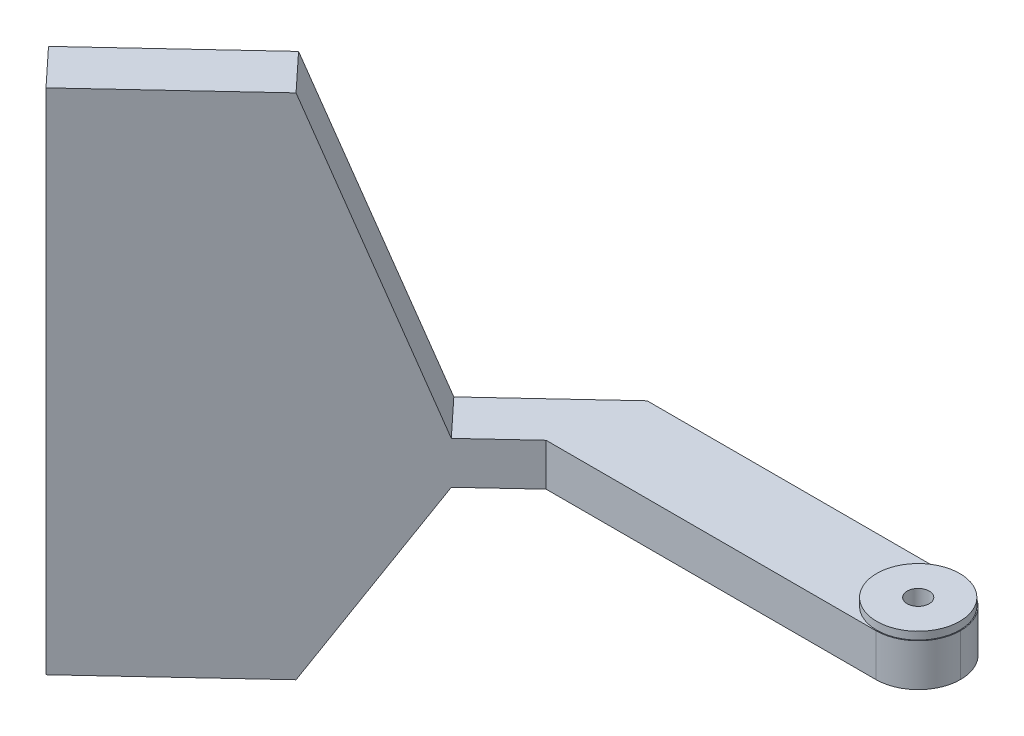
SolidWorks part; units mm, degrees
ref_plane "Front" through (0, 0, 0) normal (0, 0, 1) x (1, 0, 0)
ref_plane "Top" through (0, 0, 0) normal (0, 1, 0) x (1, 0, 0)
ref_plane "Right" through (0, 0, 0) normal (1, 0, 0) x (0, 0, -1)
sketch "Sketch1" plane through (0, 0, 0) normal (0, 1, 0) x (1, 0, 0)
  line L0 (0, 10) -> (0, 0)
  line L1 (0, 0) -> (42, 0)
  line L3 (0, 10) -> (42, 10)
  line L4 (42, 0) -> (42, 10)
  line L9 (0, 10) -> (-36.5677, -24.0999)
  line L10 (-36.5677, -24.0999) -> (-32.4757, -28.488)
  line L11 (0, 10) -> (4.092, 5.6119)
  line L12 (-32.4757, -28.488) -> (4.092, 5.6119)
  line L13 (0, 0) -> (-1.926, 0)
  line L14 (-1.926, 0) -> (0, 1.796)
  line L15 (0, 1.796) -> (0, 0)
  dimension "D1" = 10
  dimension "D2" = 42
  dimension "D3" = 223
  dimension "D4" = 50
  dimension "D5" = 6
  dimension "D6" = 270
extrude "Boss-Extrude1" add sketch "Sketch1" along normal blind 5 contours L10 L12 L1 L0 L9 | L1 L12 L11 L0 | L12 L1 L4 L3 L11 | L13 L0 L12 region at (1.364, 0, -5.8026) region at (-17.2811, 0, 10.1358) region at (21.8174, 0, -4.9666) region at (-0.642, 0, -0.5987)
fillet "Fillet1" radius 5 2 edges at (42, 2.5, 0) (42, 2.5, -10)
sketch "Sketch2" plane through (0, 5, 0) normal (0, 1, 0) x (1, 0, 0)
  circle A0 centre (37, 5) radius 1.3
extrude "Cut-Extrude1" cut sketch "Sketch2" against normal blind 10
sketch "Sketch3" plane through (0, 5, 0) normal (0, 1, 0) x (1, 0, 0)
  line L0 (-36.5677, -24.0999) -> (-32.4757, -28.488)
  line L1 (-32.4757, -28.488) -> (-17.2009, -14.244)
  line L2 (-32.4757, -28.488) -> (-1.926, 0) construction
  line L3 (-17.2009, -14.244) -> (-21.2928, -9.8559)
  line L4 (0, 10) -> (-36.5677, -24.0999) construction
  line L5 (-21.2928, -9.8559) -> (-36.5677, -24.0999)
extrude "Boss-Extrude2" add sketch "Sketch3" along normal blind 35
sketch "Sketch4" plane through (0, 0, 0) normal (0, -1, 0) x (1, 0, 0)
  line L0 (-36.5677, 24.0999) -> (-32.4757, 28.488)
  line L1 (-32.4757, 28.488) -> (-17.2009, 14.244)
  line L2 (-32.4757, 28.488) -> (-1.926, 0) construction
  line L3 (-17.2009, 14.244) -> (-21.2928, 9.8559)
  line L4 (0, -10) -> (-36.5677, 24.0999) construction
  line L5 (-21.2928, 9.8559) -> (-36.5677, 24.0999)
extrude "Boss-Extrude3" add sketch "Sketch4" along normal blind 20
sketch "Sketch5" plane through (-4.9878, 0, -5.3488) normal (-0.682, 0, -0.7314) x (-0.7314, 0, 0.682)
  line L0 (22.2943, -20) -> (22.2943, 0)
  line L1 (22.2943, 0) -> (9.3264, 0)
  line L2 (-6.82, 0) -> (22.2943, 0) construction
  line L3 (9.3264, 0) -> (22.2943, -20)
  line L4 (9.3264, 5) -> (22.2943, 40)
  line L5 (-6.82, 5) -> (22.2943, 5) construction
  line L6 (22.2943, 40) -> (22.2943, 5)
  line L7 (22.2943, 5) -> (9.3264, 5)
extrude "Boss-Extrude4" add sketch "Sketch5" against normal blind 6
sketch "Sketch6" plane through (0, 5, 0) normal (0, 1, 0) x (1, 0, 0)
  circle A1 centre (37, 5) radius 1.3
  circle A2 centre (37, 5) radius 4.9
extrude "Boss-Extrude5" add sketch "Sketch6" along normal blind 0.9
